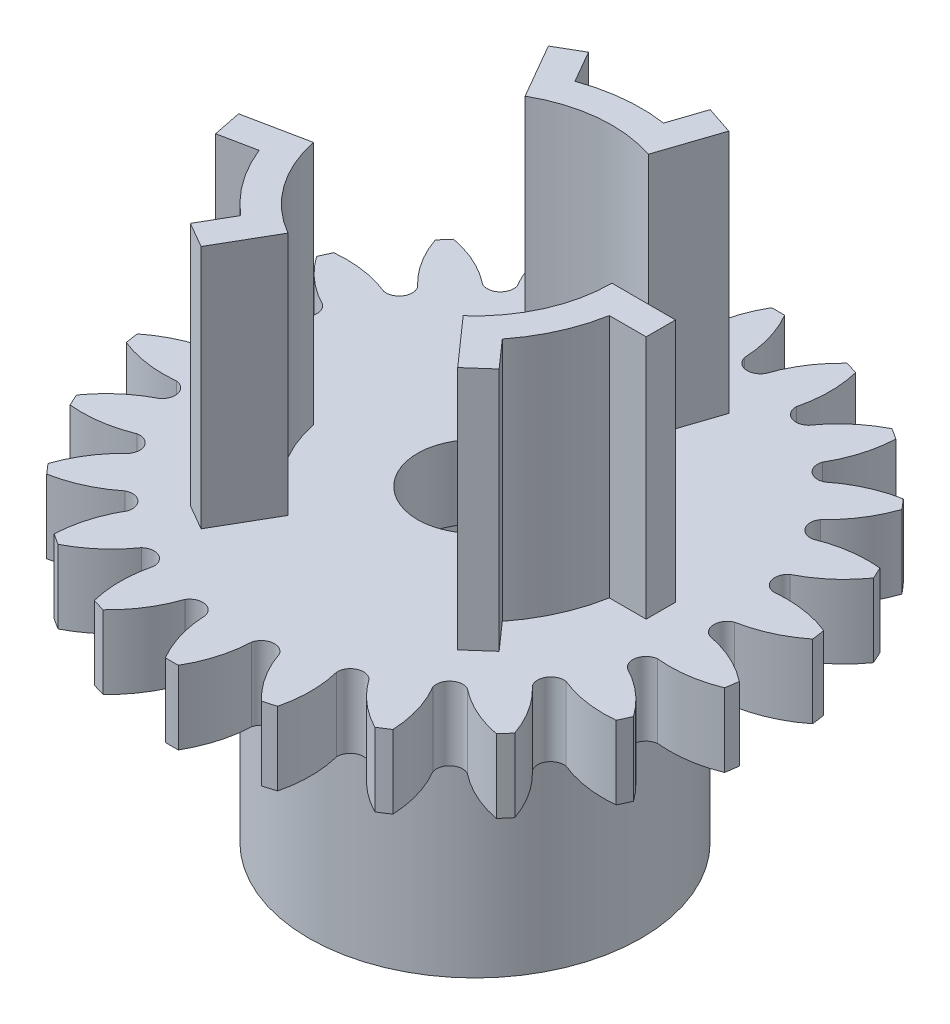
SolidWorks part; units mm, degrees
ref_plane "Front Plane" through (0, 0, 0) normal (0, 0, 1) x (1, 0, 0)
ref_plane "Top Plane" through (0, 0, 0) normal (0, 1, 0) x (1, 0, 0)
ref_plane "Right Plane" through (0, 0, 0) normal (1, 0, 0) x (0, 0, -1)
sketch "Sketch1" plane through (0, 0, 0) normal (0, 1, 0) x (1, 0, 0)
  circle A0 centre (0, 0) radius 6.8
  dimension "D1" = 13.6
extrude "Boss-Extrude1" add sketch "Sketch1" along normal blind 12.6
sketch "Sketch2" plane through (0, 0, 0) normal (0, -1, 0) x (1, 0, 0)
  circle A0 centre (0, 0) radius 5.8
  dimension "D1" = 11.6
extrude "Cut-Extrude1" cut sketch "Sketch2" against normal through all
sketch "Sketch3" plane through (0, 12.6, 0) normal (0, 1, 0) x (1, 0, 0)
  circle A0 centre (0, 0) radius 12.4
  dimension "D1" = 24.8
extrude "Boss-Extrude3" add sketch "Sketch3" against normal blind 3
sketch "Sketch4" plane through (0, 12.6, 0) normal (0, 1, 0) x (1, 0, 0)
  circle A0 centre (0, 0) radius 2.35
  dimension "D1" = 4.7
extrude "Cut-Extrude2" cut sketch "Sketch4" against normal up to surface (3 mm away) up to face at (0, 9.6, 5.8)
sketch "Sketch5" plane through (0, 12.6, 0) normal (0, 1, 0) x (1, 0, 0)
  line L0 (-12.4, 0) -> (12.4, 0) construction
  line L1 (12.3089, 1.5) -> (12.3089, -1.5) construction
  line L2 (10.1089, 0.5) -> (10.1089, -0.5) construction
  circle A0 centre (0, 0) radius 12.4 construction
  arc A1 (12.3089, -1.5) -> (12.3089, 1.5) centre (0, 0) ccw
  arc A2 (10.1089, 0.5) -> (10.1089, -0.5) centre (10.3134, 0) ccw
  arc A8 (10.1089, 0.5) -> (12.3089, 1.5) centre (9.1909, 5.4397) ccw
  arc A9 (10.1089, -0.5) -> (12.3089, -1.5) centre (9.1909, -5.4397) cw
  point P5 (12.4, 0)
  point P7 (10.3134, 0)
  point P10 (10.1089, 0)
  dimension "D1" = 3
  dimension "D2" = 1
  dimension "D3" = 2.2
extrude "Cut-Extrude3" cut sketch "Sketch5" against normal up to surface (3 mm away) up to face at (0, 9.6, 12.4)
ref_axis "Axis1" through (0, 13.23, 0) along (0, -1, 0)
pattern_circular "CirPattern1" count 22 over 360 about axis through (0, 13.23, 0) along (0, -1, 0) of "Cut-Extrude3"
sketch "Sketch6" plane through (0, 12.6, 0) normal (0, 1, 0) x (1, 0, 0)
  line L0 (0, 0) -> (5.6, 0) construction
  line L1 (5.6, 0) -> (3.7107, -4.1941) construction
  line L2 (0, 0) -> (33131.3776, -37447.4541) construction
  line L3 (8.2, 0) -> (5.6, 0)
  line L4 (8.2, 0) -> (8.2, -1.2)
  line L5 (8.2, -1.2) -> (6.6933, -1.2)
  line L6 (3.7107, -4.1941) -> (5.4335, -6.1414)
  line L7 (5.4335, -6.1414) -> (6.3323, -5.3462)
  line L8 (6.3323, -5.3462) -> (5.3339, -4.2178)
  line L9 (-8.0354, -1.6349) -> (-7.7961, -2.8108)
  line L10 (-7.7961, -2.8108) -> (-6.3196, -2.5104)
  line L11 (-5.1392, -6.5014) -> (-4.3859, -5.1966)
  line L12 (-4.1, -7.1014) -> (-5.1392, -6.5014)
  line L13 (-4.1, -7.1014) -> (-2.8, -4.8497)
  line L14 (-5.4876, -1.1165) -> (-8.0354, -1.6349)
  line L15 (2.6018, 7.7763) -> (1.4638, 8.157)
  line L16 (1.4638, 8.157) -> (0.9858, 6.7282)
  line L17 (-3.0608, 7.7014) -> (-2.3074, 6.3966)
  line L18 (-4.1, 7.1014) -> (-3.0608, 7.7014)
  line L19 (-4.1, 7.1014) -> (-2.8, 4.8497)
  line L20 (1.7769, 5.3106) -> (2.6018, 7.7763)
  arc A0 (6.6933, -1.2) -> (5.3339, -4.2178) centre (0, 0) cw
  arc A1 (5.6, 0) -> (3.7107, -4.1941) centre (0, 0) cw
  arc A2 (-4.3859, -5.1966) -> (-6.3196, -2.5104) centre (0, 0) cw
  arc A3 (-2.8, -4.8497) -> (-5.4876, -1.1165) centre (0, 0) cw
  arc A4 (-2.3074, 6.3966) -> (0.9858, 6.7282) centre (0, 0) cw
  arc A5 (-2.8, 4.8497) -> (1.7769, 5.3106) centre (0, 0) cw
  point P31 (0, 0)
  dimension "D1" = 6.8
  dimension "D2" = 5.6
  dimension "D3" = 4.6
  dimension "D4" = 2.6
  dimension "D5" = 1.2
  dimension "D6" = 3
extrude "Boss-Extrude4" add sketch "Sketch6" along normal blind 10
equation "\"12.6`\"=10"
